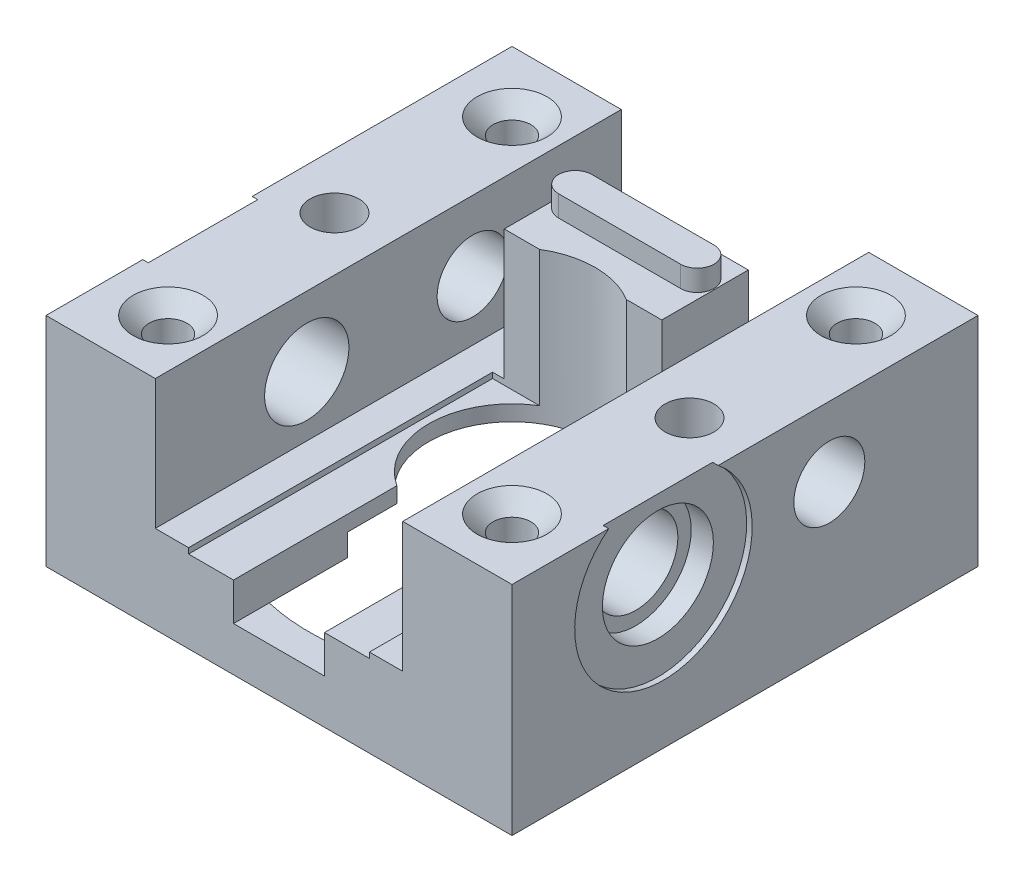
SolidWorks part; units mm, degrees
ref_plane "Alzado" through (0, 0, 0) normal (0, 0, 1) x (1, 0, 0)
ref_plane "Planta" through (0, 0, 0) normal (0, 1, 0) x (1, 0, 0)
ref_plane "Vista lateral" through (0, 0, 0) normal (1, 0, 0) x (0, 0, -1)
sketch "Croquis3" plane through (0, 0, 0) normal (0, 1, 0) x (1, 0, 0)
  line L1 (-21, 21) -> (21, 21)
  line L2 (-21, 21) -> (-21, -21)
  line L3 (-21, -21) -> (21, -21)
  line L4 (21, 21) -> (21, -21)
  line L5 (-21, 21) -> (21, -21) construction
  line L6 (-21, -21) -> (21, 21) construction
  point P0 (0, 0)
  dimension "D1" = 42
  dimension "D2" = 42
extrude "Saliente-Extruir1" add sketch "Croquis3" against normal blind 19.6
sketch "Croquis4" plane through (0, 0, 0) normal (0, 1, 0) x (1, 0, 0)
  line L0 (0, 21) -> (0, -21) construction
  line L1 (21, 21) -> (-21, 21) construction
  line L2 (-21, -21) -> (21, -21) construction
  line L3 (-11.15, 21) -> (-11.15, -21)
  line L4 (11.15, 21) -> (11.15, -21)
  line L5 (-11.15, 21) -> (11.15, 21)
  line L6 (-11.15, -21) -> (11.15, -21)
  line L7 (-7.1, 14.2) -> (7.1, 14.2)
  line L8 (-7.1, 14.2) -> (-7.1, 6.4)
  line L9 (7.1, 14.2) -> (7.1, 6.4)
  line L10 (-7.1, 6.4) -> (7.1, 6.4)
  line L12 (-7.1, 21) -> (-7.1, -21) construction
  line L13 (7.1, 21) -> (7.1, -21) construction
  line L14 (-11.15, 14.2) -> (11.15, 14.2) construction
  line L15 (-11.15, 6.4) -> (11.15, 6.4) construction
  dimension "D1" = 11.15
  dimension "D2" = 11.15
  dimension "D3" = 6.8
  dimension "D4" = 7.1
  dimension "D5" = 7.1
  dimension "D6" = 7.8
extrude "Cortar-Extruir1" cut sketch "Croquis4" against normal blind 11.7
sketch "Croquis5" plane through (0, -11.7, 0) normal (0, 1, 0) x (1, 0, 0)
  line L4 (-8.15, 21) -> (-8.15, 14.2)
  line L5 (8.15, -21) -> (8.15, 6.4)
  line L6 (-7.1, 6.4) -> (7.1, 6.4) construction
  line L7 (-8.15, 6.4) -> (8.15, 6.4)
  line L8 (7.1, 14.2) -> (-7.1, 14.2) construction
  line L9 (8.15, 14.2) -> (-8.15, 14.2)
  line L10 (-8.15, 6.4) -> (-8.15, -21)
  line L11 (8.15, 14.2) -> (8.15, 21)
  line L13 (-8.15, 21) -> (8.15, 21)
  line L15 (-8.15, -21) -> (8.15, -21)
extrude "Cortar-Extruir2" cut sketch "Croquis5" against normal blind 0.5
sketch "Croquis6" plane through (0, -12.2, 0) normal (0, 1, 0) x (1, 0, 0)
  line L0 (0, -21) -> (0, 21) construction
  line L1 (-8.15, -21) -> (8.15, -21) construction
  line L2 (8.15, 21) -> (-8.15, 21) construction
  line L3 (4.1, -21) -> (4.1, -6.2801)
  line L4 (-4.1, -21) -> (-4.1, -6.2801)
  line L7 (-4.1, -21) -> (-4.1, 21) construction
  line L8 (-4.1, -21) -> (4.1, -21)
  line L9 (4.1, -21) -> (4.1, 21) construction
  arc A0 (4.1, -6.2801) -> (-4.1, -6.2801) centre (0, 0) ccw
  dimension "D3" = 15
  dimension "D1" = 4.1
  dimension "D2" = 4.1
extrude "Cortar-Extruir3" cut sketch "Croquis6" against normal blind 3.4 and the other way up to surface (12.2 mm away) contours A0 L4 L8 L3 other way up to face at (0, 0, -10.3)
sketch "Croquis7" plane through (0, -19.6, 0) normal (0, -1, 0) x (1, 0, 0)
  circle A0 centre (0, 0) radius 18.25
  dimension "D1" = 36.5
extrude "Cortar-Extruir4" cut sketch "Croquis7" against normal blind 4
sketch "Croquis8" plane through (0, -15.6, 0) normal (0, -1, 0) x (1, 0, 0)
  circle A0 centre (0, 0) radius 11.5
  dimension "D1" = 23
extrude "Cortar-Extruir5" cut sketch "Croquis8" against normal blind 2
sketch "Croquis9" plane through (0, -15.6, 0) normal (0, -1, 0) x (1, 0, 0)
  line L0 (-21, 0) -> (21, 0) construction
  line L1 (-21, -21) -> (-21, 21) construction
  line L2 (21, 21) -> (21, -21) construction
  line L3 (0, 21) -> (0, -21) construction
  line L4 (-21, 21) -> (21, 21) construction
  line L5 (21, -21) -> (-21, -21) construction
  line L6 (-16, 21) -> (-16, -21) construction
  line L7 (16, 21) -> (16, -21) construction
  circle A0 centre (-16, 0) radius 2.2
  circle A1 centre (16, 0) radius 2.2
  dimension "D3" = 4.4
  dimension "D4" = 4.4
  dimension "D1" = 16
  dimension "D2" = 16
extrude "Cortar-Extruir6" cut sketch "Croquis9" against normal up to surface (15.6 mm away) up to face at (-16.075, 0, 0)
hole_wizard "Avellanado para tornillo con cabeza plana avellanada de M31" positions "Croquis11" profile "Croquis10" countersink size "M3" standard "ISO" end condition through all
sketch "Croquis11" plane through (0, 0, 0) normal (0, 1, 0) x (1, 0, 0)
  line L0 (-11.15, 21) -> (-21, 21) construction
  line L2 (-21, 21) -> (-21, -21) construction
  point P0 (-15.5, 15.5)
  point P2 (15.5, 15.5)
  point P4 (15.5, -15.5)
  point P6 (-15.5, -15.5)
  dimension "D1" = 31
  dimension "D2" = 31
  dimension "D3" = 5.5
  dimension "D4" = 5.5
sketch "Croquis10" plane through (-15.5, 0, -15.5) normal (1, 0, 0) x (0, 0, 1)
  line L0 (0, 0) -> (0, 19.6)
  line L1 (0, 19.6) -> (1.7, 19.6)
  line L2 (1.7, 19.6) -> (1.7, 1.45)
  line L3 (1.7, 1.45) -> (3.15, 0)
  line L5 (3.15, 0) -> (0, 0)
  line L6 (-1.7, 1.45) -> (-3.15, 0) construction
  line L11 (0, -6.35) -> (0, 107.95) construction
  dimension "Diámetro de taladro hasta el siguiente" = 3.4
  dimension "Profundidad de taladro hasta el siguiente" = 19.6
  dimension "Diámetro de avellanado cercano" = 6.3
  dimension "Ángulo de avellanado cercano" = 90
sketch "Croquis12" plane through (0, 0, 0) normal (0, 1, 0) x (1, 0, 0)
  line L1 (0, 14.2) -> (0, 7.5) construction
  line L2 (7.1, 11.2) -> (-7.1, 11.2) construction
  line L3 (7.1, 14.2) -> (-7.1, 14.2) construction
  line L4 (-5.5, 11.2) -> (5.5, 11.2) construction
  line L5 (-5.5, 12.7) -> (5.5, 12.7)
  line L6 (-5.5, 9.7) -> (5.5, 9.7)
  arc A0 (3.9102, 6.4) -> (-3.9102, 6.4) centre (0, 0) ccw construction
  arc A1 (-5.5, 12.7) -> (-5.5, 9.7) centre (-5.5, 11.2) ccw
  arc A2 (5.5, 9.7) -> (5.5, 12.7) centre (5.5, 11.2) ccw
  point P11 (0, 11.2)
  dimension "D1" = 3
extrude "Saliente-Extruir3" add sketch "Croquis12" along normal blind 1.9
sketch "Croquis13" plane through (21, 0, 0) normal (1, 0, 0) x (0, 0, -1)
  line L2 (-7.35, -19.6) -> (-7.35, 0)
  line L3 (-7.35, -19.6) -> (-7.35, 0) construction
  line L5 (-21, -6.3) -> (21, -6.3)
  line L6 (-21, -6.3) -> (21, -6.3) construction
  circle A0 centre (-7.35, -6.3) radius 8
  dimension "D3" = 16
  dimension "D1" = 13.65
  dimension "D2" = 6.3
extrude "Cortar-Extruir7" cut sketch "Croquis13" against normal blind 0.5
sketch "Croquis14" plane through (20.5, 0, 0) normal (1, 0, 0) x (0, 0, -1)
  line L0 (-7.35, -14.3) -> (-7.35, 0) construction
  line L1 (-12.2805, 0) -> (-2.4195, 0) construction
  line L2 (-15.35, -6.3) -> (0.65, -6.3) construction
  arc A0 (-12.2805, 0) -> (-2.4195, 0) centre (-7.35, -6.3) ccw construction
  arc A1 (-12.2805, 0) -> (-2.4195, 0) centre (-7.35, -6.3) ccw construction
  circle A2 centre (-7.35, -6.3) radius 5
extrude "Cortar-Extruir8" cut sketch "Croquis14" against normal blind 2
hole_wizard "Diámetro de taladro Ø7.6 (7.6)1" positions "Croquis16" profile "Croquis15" hole size "Ø7.6" standard "ISO" end condition through all
sketch "Croquis16" plane through (18.5, 0, 0) normal (1, 0, 0) x (0, 0, -1)
  point P0 (-7.35, -6.3)
sketch "Croquis15" plane through (18.5, -6.3, 7.35) normal (0, 1, 0) x (0, 0, -1)
  line L0 (0, 0) -> (0, 39.5)
  line L1 (0, 39.5) -> (3.8, 39.5)
  line L2 (3.8, 39.5) -> (3.8, 0)
  line L5 (3.8, 0) -> (0, 0)
  line L11 (0, -6.35) -> (0, 107.95) construction
  dimension "Diámetro de taladro hasta el siguiente" = 7.6
  dimension "Profundidad de taladro hasta el siguiente" = 39.5
sketch "Croquis17" plane through (-21, 0, 0) normal (-1, 0, 0) x (0, 0, 1)
  circle A0 centre (7.35, -6.3) radius 8
extrude "Cortar-Extruir9" cut sketch "Croquis17" against normal blind 0.5
sketch "Croquis18" plane through (-20.5, 0, 0) normal (-1, 0, 0) x (0, 0, 1)
  circle A0 centre (7.35, -6.3) radius 5
extrude "Cortar-Extruir10" cut sketch "Croquis18" against normal blind 2
sketch "Croquis19" plane through (0, 0, -14.2) normal (0, 0, -1) x (-1, 0, 0)
  line L10 (-7.1, -6.2) -> (7.1, -6.2)
  line L11 (-7.1, -6.2) -> (7.1, -6.2) construction
  line L13 (-4, -11.7) -> (-4, 0)
  line L14 (-4, -11.7) -> (-4, 0) construction
  line L16 (4, -11.7) -> (4, 0)
  line L17 (4, -11.7) -> (4, 0) construction
  circle A0 centre (4, -6.2) radius 2.7
  circle A1 centre (-4, -6.2) radius 2.7
  dimension "D4" = 8
  dimension "D1" = 6.2
  dimension "D2" = 3.1
  dimension "D3" = 3.1
extrude "Cortar-Extruir11" cut sketch "Croquis19" against normal blind 4.9
sketch "Croquis20" plane through (-21, 0, 0) normal (-1, 0, 0) x (0, 0, 1)
  line L0 (3.55, -6.3) -> (-24.8673, -6.3) construction
  line L3 (-7.6, -19.6) -> (-7.6, 0)
  line L4 (-7.6, -19.6) -> (-7.6, 0) construction
  circle A0 centre (7.35, -6.3) radius 3.8 construction
  dimension "D1" = 13.4
hole_wizard "Diámetro de taladro Ø6.4 (6.4)1" positions "Croquis22" profile "Croquis21" hole size "Ø6.4" standard "ISO" end condition up to next
sketch "Croquis22" plane through (-21, 0, 0) normal (-1, 0, 0) x (0, 0, 1)
  line L0 (3.55, -6.3) -> (-24.8673, -6.3) construction
  line L1 (-7.6, -19.6) -> (-7.6, 0) construction
  point P0 (-7.6, -6.3)
sketch "Croquis21" plane through (-21, -6.3, -7.6) normal (0, 1, 0) x (0, 0, 1)
  line L0 (0, 0) -> (0, 9.85)
  line L1 (0, 9.85) -> (3.2, 9.85)
  line L2 (3.2, 9.85) -> (3.2, 0)
  line L5 (3.2, 0) -> (0, 0)
  line L11 (0, -6.35) -> (0, 107.95) construction
  dimension "Diámetro de taladro hasta el siguiente" = 6.4
  dimension "Profundidad de taladro hasta el siguiente" = 9.85
hole_wizard "Diámetro de taladro Ø6.4 (6.4)2" positions "Croquis24" profile "Croquis23" hole size "Ø6.4" standard "ISO" end condition up to next
sketch "Croquis24" plane through (21, 0, 0) normal (1, 0, 0) x (0, 0, -1)
  line L0 (-3.55, -6.3) -> (24.8673, -6.3) construction
  line L1 (7.6, -19.6) -> (7.6, 0) construction
  point P2 (7.6, -6.3)
sketch "Croquis23" plane through (21, -6.3, -7.6) normal (0, 1, 0) x (0, 0, -1)
  line L0 (0, 0) -> (0, 9.85)
  line L1 (0, 9.85) -> (3.2, 9.85)
  line L2 (3.2, 9.85) -> (3.2, 0)
  line L5 (3.2, 0) -> (0, 0)
  line L11 (0, -6.35) -> (0, 107.95) construction
  dimension "Diámetro de taladro hasta el siguiente" = 6.4
  dimension "Profundidad de taladro hasta el siguiente" = 9.85
equation "\"D4@Croquis9\"=\"D3@Croquis9\""
